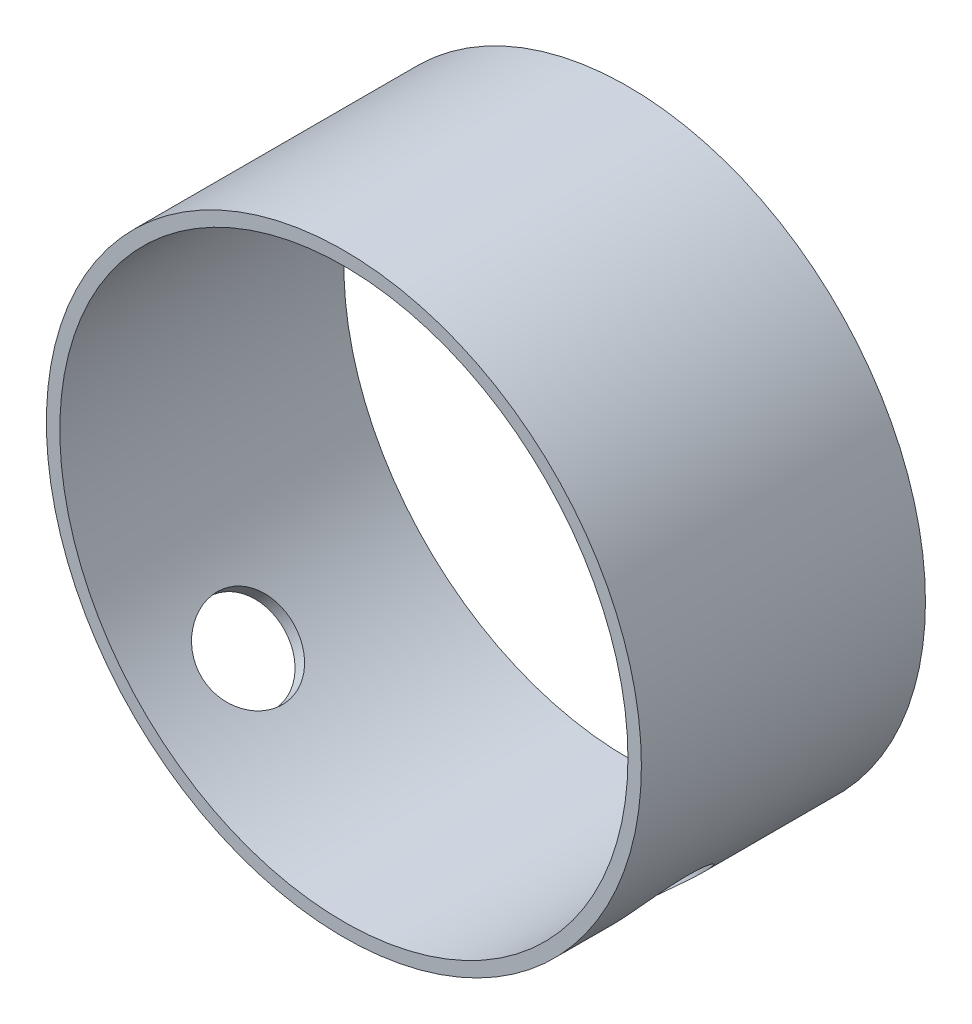
SolidWorks part; units mm, degrees
ref_plane "Front Plane" through (0, 0, 0) normal (0, 0, 1) x (1, 0, 0)
ref_plane "Top Plane" through (0, 0, 0) normal (0, 1, 0) x (1, 0, 0)
ref_plane "Right Plane" through (0, 0, 0) normal (1, 0, 0) x (0, 0, -1)
sketch "Sketch1" plane through (0, 0, 0) normal (0, 0, 1) x (1, 0, 0)
  circle A0 centre (0, 0) radius 39.9034
  circle A1 centre (0, 0) radius 38.1
  dimension "D1" = 76.2
  dimension "D2" = 79.8068
extrude "Boss-Extrude1" add sketch "Sketch1" along normal mid plane 38.1
ref_axis "Axis1" through (0, 0, -127.4763) along (0, 0, 1)
ref_plane "Plane1" through (0, 0, 0) normal (-0.7071, 0.7071, 0) x (0, 0, 1)
sketch "Sketch2" plane through (0, 0, 0) normal (-0.7071, 0.7071, 0) x (0, 0, 1)
  circle A0 centre (5.08, 0) radius 6.1849
extrude "Cut-Extrude1" cut sketch "Sketch2" against normal through all
ref_plane "Plane2" through (0, 0, 0) normal (-0.7071, -0.7071, 0) x (0, 0, 1)
sketch "Sketch3" plane through (0, 0, 0) normal (-0.7071, -0.7071, 0) x (0, 0, 1)
  circle A0 centre (5.08, 0) radius 6.1849
extrude "Cut-Extrude2" cut sketch "Sketch3" along normal through all
equation "\"AIRFRAME_OD\"= 3.142in"
equation "\"AIRFRAME_ID\"= 3.00in"
equation "\"FLAT_T\"= 0.125in"
equation "\"NOSE_EXP_L\"= 3.5in"
equation "\"NOSE_SHOULDER_L\"= 5in"
equation "\"MAIN_L\"= 30in"
equation "\"RECO_COUP_L\"= 6in"
equation "\"RECO_SWITCH_L\"= 1.5in"
equation "\"DROGUE_L\"= 14in"
equation "\"ATS_FORE_COUP_L\"= 4in"
equation "\"ATS_AFT_COUP_L\"= 2.5in"
equation "\"LOWER_L\"= 16in"
equation "\"FIN_N\"= 4"
equation "\"CR_AFT_X\"= 0.5in"
equation "\"CR_FORE_X\"= 6in"
equation "\"D1@Sketch1\"=\"AIRFRAME_ID\""
equation "\"D2@Sketch1\"=\"AIRFRAME_OD\""
equation "\"D1@Boss-Extrude1\"=\"RECO_SWITCH_L\""
equation "\"FIN_ROOT\"= 5in"
equation "\"FIN_X\"= 0.75in"
equation "\"MOTOR_OD\"= 2.25in"
equation "\"MOTOR_ID\"= 2.126in"
